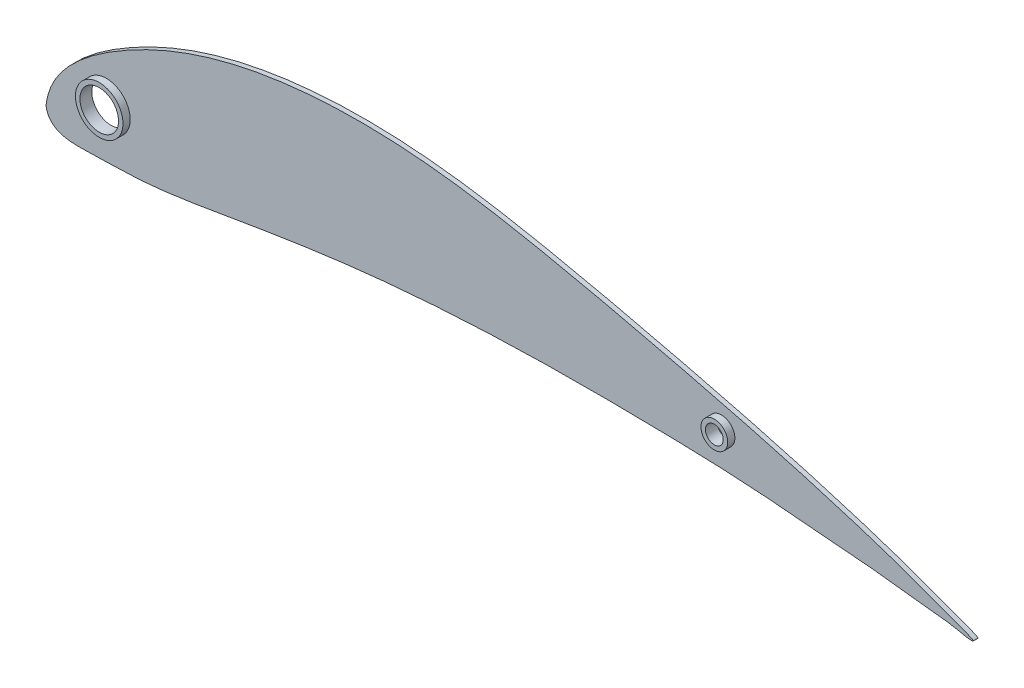
SolidWorks part; units mm, degrees
material "ABS"
ref_plane "Front Plane" through (0, 0, 0) normal (0, 0, 1) x (1, 0, 0)
ref_plane "Top Plane" through (0, 0, 0) normal (0, 1, 0) x (1, 0, 0)
ref_plane "Right Plane" through (0, 0, 0) normal (1, 0, 0) x (0, 0, -1)
sketch "Sketch1" plane through (0, 0, 0) normal (0, 0, 1) x (1, 0, 0)
  spline S0 degree 3 poles (0.0006, 0.0001) (0.8106, 7.3592) (8.6491, 17.8566) (26.2867, 29.9752) (52.1111, 42.0692) (89.5976, 49.2908) (131.4008, 47.8848) (173.2567, 40.0411) (217.9611, 29.613) (256.9521, 19.5289) (290.3598, 8.711) (301.2732, 4.3828) (314.8169, -0.5162) (309.8463, 0.0001) knots 0 0 0 0 0.060864 0.113688 0.188609 0.312909 0.448482 0.557612 0.691544 0.852438 0.929756 0.976058 1 1 1 1
  spline S1 degree 3 poles (309.8463, 0.0001) (303.9568, 1.471) (293.9895, 2.094) (276.264, 4.5144) (260.8463, 5.4274) (235.8588, 7.8703) (205.1014, 8.8381) (157.7186, 9.0307) (110.4973, 6.1815) (66.5062, -0.5867) (36.4547, -6.0985) (15.3166, -6.1891) (1.2307, -6.9241) (0.0006, 0.0001) knots 0 0 0 0 0.057787 0.095275 0.171021 0.205339 0.335319 0.464904 0.658702 0.785512 0.893517 0.943092 1 1 1 1
extrude "Boss-Extrude1" add sketch "Sketch1" along normal blind 1.5875
sketch "Sketch2" plane through (0, 0, 1.5875) normal (0, 0, 1) x (1, 0, 0)
  circle A0 centre (20.32, 10.16) radius 6.5
  circle A1 centre (227.2963, 19.0501) radius 3
  circle A2 centre (20.32, 10.16) radius 5.75
  circle A3 centre (20.32, 10.16) radius 8
  circle A4 centre (227.2963, 19.0501) radius 4.5
  circle A5 centre (227.2963, 19.0501) radius 2.5
  dimension "D2" = 13
  dimension "D3" = 6
  dimension "D6" = 20.32
  dimension "D7" = 1.5
  dimension "D8" = 11.5
  dimension "D9" = 5
  dimension "D10" = 1.5
  dimension "D1" = 82.55
  dimension "D4" = 19.05
  dimension "D5" = 10.16
extrude "Boss-Extrude2" add sketch "Sketch2" along normal blind 2.4125 contours A4 A1 | A3 A0 region at (12.5463, 10.16, 1.5875) region at (222.9236, 19.0501, 1.5875)
extrude "Cut-Extrude1" cut sketch "Sketch2<4>" against normal blind 4 contours A2 | A0 A2 | A1 region at (14.0038, 10.16, 1.5875) region at (20.32, 10.16, 1.5875)
sketch "Sketch2<4>" plane through (0, 0, 1.5875) normal (0, 0, 1) x (1, 0, 0) same geometry as "Sketch2"
